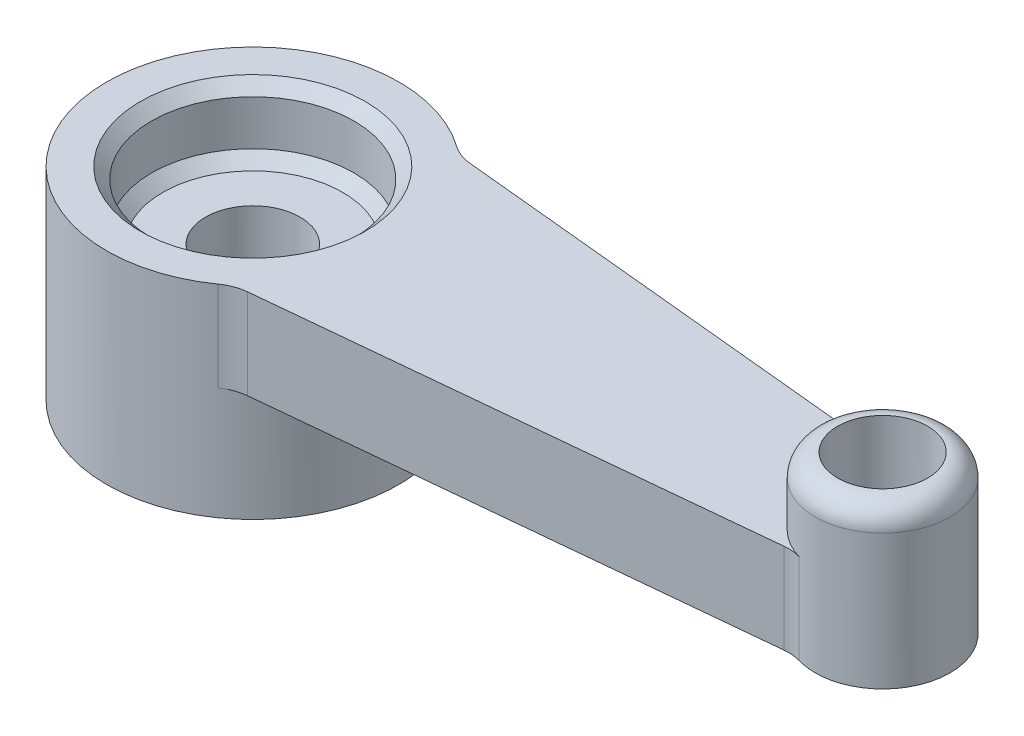
SolidWorks part; units mm, degrees
material "Plain Carbon Steel"
ref_plane "Front Plane" through (0, 0, 0) normal (0, 0, 1) x (1, 0, 0)
ref_plane "Top Plane" through (0, 0, 0) normal (0, 1, 0) x (1, 0, 0)
ref_plane "Right Plane" through (0, 0, 0) normal (1, 0, 0) x (0, 0, -1)
sketch "Sketch1" plane through (0, 0, 0) normal (0, 1, 0) x (1, 0, 0)
  line L0 (2.3599, 2.4722) -> (13.2145, 1.4083)
  line L1 (2.3599, -2.4722) -> (13.2145, -1.4083)
  arc A1 (13.5873, -1.4421) -> (13.5873, 1.4421) centre (14, 0) ccw
  arc A2 (1.8792, 2.6516) -> (1.8792, -2.6516) centre (0, 0) ccw
  arc A3 (13.2145, -1.4083) -> (13.5873, -1.4421) centre (13.3121, -2.4035) cw
  arc A4 (13.2145, 1.4083) -> (13.5873, 1.4421) centre (13.3121, 2.4035) ccw
  arc A5 (1.8792, -2.6516) -> (2.3599, -2.4722) centre (2.4575, -3.4675) cw
  arc A6 (1.8792, 2.6516) -> (2.3599, 2.4722) centre (2.4575, 3.4675) ccw
  point P21 (14.8292, -1.25)
  point P24 (14.8292, 1.25)
  point P27 (2.0767, -2.5)
  point P30 (2.0767, 2.5)
  dimension "D1" = 6.5
  dimension "D2" = 3
  dimension "D6" = 1
  dimension "D3" = 14
  dimension "D4" = 5
  dimension "D5" = 2.5
extrude "Boss-Extrude1" add sketch "Sketch1" along normal mid plane 2
sketch "Sketch2" plane through (0, 1, 0) normal (0, 1, 0) x (1, 0, 0)
  circle A0 centre (0, 0) radius 3.25
  arc A1 (1.8792, 2.6516) -> (1.8792, -2.6516) centre (0, 0) ccw construction
extrude "Boss-Extrude2" add sketch "Sketch2" against normal blind 4.5
sketch "Sketch3" plane through (0, -1, 0) normal (0, -1, 0) x (1, 0, 0)
  circle A0 centre (14, 0) radius 1.5
  arc A1 (13.5873, -1.4421) -> (13.5873, 1.4421) centre (14, 0) ccw construction
extrude "Boss-Extrude3" add sketch "Sketch3" against normal blind 3.5
sketch "Sketch9" plane through (0, 2.5, 0) normal (0, 1, 0) x (1, 0, 0)
  point P0 (14, 0)
hole_wizard "Ø2.0mm Dowel Hole2" positions "Sketch9" profile "Sketch8" hole size "Ø2.0" standard "ANSI Metric"
sketch "Sketch8" plane through (14, 2.5, 0) normal (1, 0, 0) x (0, 0, 1)
  line L0 (0, 0) -> (0, 3)
  line L1 (0, 3) -> (1, 2.3991)
  line L2 (1, 2.3991) -> (1, 0)
  line L5 (1, 0) -> (0, 0)
  line L10 (0, 3) -> (-1, 2.3991) construction
  line L11 (0, -1.9332) -> (0, 21.2516) construction
  dimension "Hole Dia." = 2
  dimension "Hole Depth" = 3
  dimension "Drill Angle" = 118
fillet "Fillet1" radius 0.5 1 edges at (14, 2.5, -1.5)
ref_plane "Plane1" through (15.5, 0, 0) normal (1, 0, 0) x (0, 0, -1)
sketch "Sketch10" plane through (0, 1, 0) normal (0, 1, 0) x (1, 0, 0)
  circle A0 centre (0, 0) radius 2.25
  dimension "D1" = 4.5
extrude "Cut-Extrude1" cut sketch "Sketch10" against normal blind 1.5 and the other way through all
sketch "Sketch12" plane through (0, -3.5, 0) normal (0, -1, 0) x (1, 0, 0)
  line L0 (1.7321, 1) -> (1.7321, -1)
  arc A0 (1.7321, 1) -> (1.7321, -1) centre (0, 0) ccw
  dimension "D1" = 4
  dimension "D2" = 2
extrude "Cut-Extrude2" cut sketch "Sketch12" against normal blind 1.5
chamfer "Chamfer1" distance 0.25 angle 45 2 edges at (0, 1, -2.25) (0, -0.5, 2.25)
sketch "Sketch15" plane through (0, -0.5, 0) normal (0, 1, 0) x (1, 0, 0)
  point P0 (0, 0)
hole_wizard "Ø2.0mm Dowel Hole1" positions "Sketch15" profile "Sketch14" hole size "Ø2.0" standard "ANSI Metric" end condition through all
sketch "Sketch14" plane through (0, -0.5, 0) normal (1, 0, 0) x (0, 0, 1)
  line L0 (0, 0) -> (0, 3)
  line L1 (0, 3) -> (1.05, 3)
  line L2 (1.05, 3) -> (1.05, 0)
  line L5 (1.05, 0) -> (0, 0)
  line L11 (0, -6.35) -> (0, 107.95) construction
  dimension "Thru Hole Dia." = 2.1
  dimension "Thru Hole Depth" = 3
ref_plane "Plane2" through (1.7321, 0, 0) normal (1, 0, 0) x (0, 0, -1)
